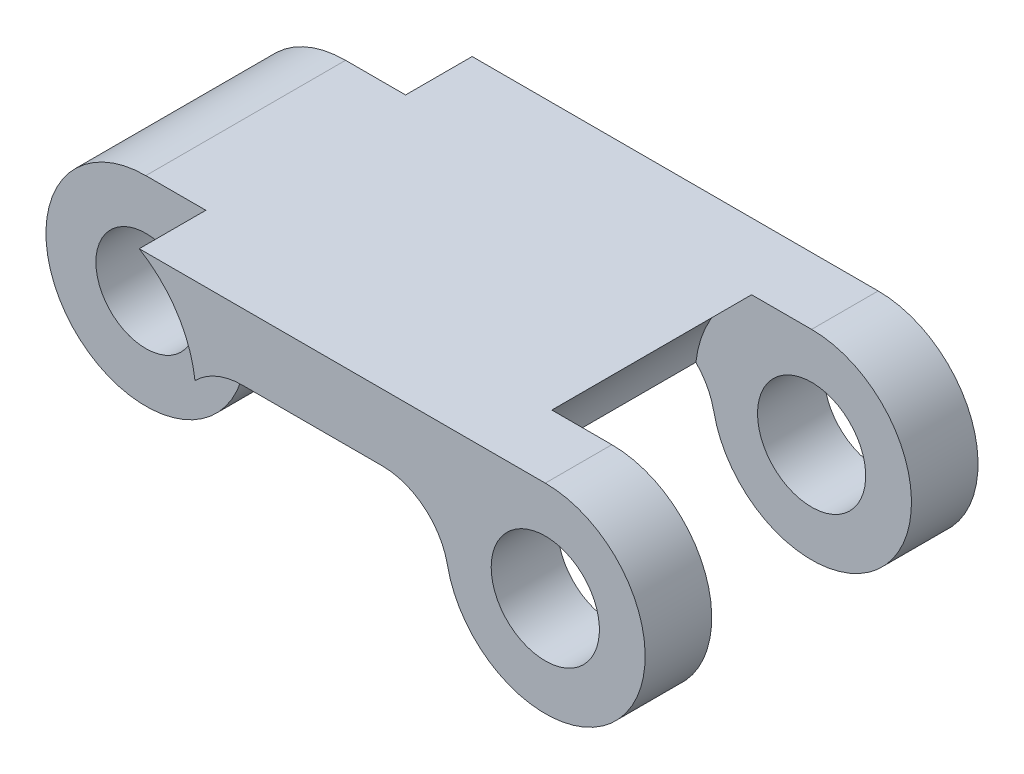
SolidWorks part; units mm, degrees
material "ABS PC"
ref_plane "Piano frontale" through (0, 0, 0) normal (0, 0, 1) x (1, 0, 0)
ref_plane "Piano superiore" through (0, 0, 0) normal (0, 1, 0) x (1, 0, 0)
ref_plane "Piano destro" through (0, 0, 0) normal (1, 0, 0) x (0, 0, -1)
sketch "Schizzo1" plane through (0, 0, 0) normal (0, 0, 1) x (1, 0, 0)
  line L0 (-24.825, 11.3137) -> (-10.825, 11.3137)
  line L1 (-21.9965, 9.3137) -> (-13.6534, 9.3137)
  arc A0 (-24.825, 11.3137) -> (-21.9965, 9.3137) centre (-24.825, 8.3137) ccw
  arc A1 (-10.825, 11.3137) -> (-13.6534, 9.3137) centre (-10.825, 8.3137) cw
  dimension "D1" = 3
  dimension "D2" = 3
  dimension "D3" = 2
  dimension "D5" = 14
extrude "Estrusione-Estrusione1" add sketch "Schizzo1" along normal blind 10
sketch "Schizzo5" plane through (0, 0, 0) normal (0, 0, -1) x (-1, 0, 0)
  circle A0 centre (10.825, 8.3137) radius 1.625
  circle A1 centre (24.825, 8.3137) radius 1.5
  arc A2 (21.9965, 9.3137) -> (24.825, 11.3137) centre (24.825, 8.3137) ccw construction
  arc A3 (10.825, 11.3137) -> (13.6534, 9.3137) centre (10.825, 8.3137) ccw construction
  dimension "D1" = 0
  dimension "D3" = 3.25
  dimension "D4" = 3
  dimension "D2" = 0
extrude "Taglio-Estrusione1" cut sketch "Schizzo5" against normal blind 10
sketch "Schizzo6" plane through (0, 0, 0) normal (0, 0, -1) x (-1, 0, 0)
  circle A0 centre (24.825, 8.3137) radius 3.5
  dimension "D1" = 7
extrude "Taglio-Estrusione2" cut sketch "Schizzo6" against normal blind 2
extrude "Taglio-Estrusione3" cut sketch "Schizzo6<2>" against normal blind 12 from offset 8 offset against normal yes
sketch "Schizzo6<2>" plane through (0, 0, 0) normal (0, 0, -1) x (-1, 0, 0) same geometry as "Schizzo6"
sketch "Schizzo7" plane through (0, 0, 0) normal (0, 0, -1) x (-1, 0, 0)
  circle A0 centre (10.825, 8.3137) radius 3.5
  dimension "D1" = 7
extrude "Taglio-Estrusione4" cut sketch "Schizzo7" against normal blind 6 from offset 2 offset against normal yes
fillet "Raccordo1" radius 2 1 edges at (-21.9965, 9.3137, 5)
fillet "Raccordo2" radius 2 1 edges at (-13.6534, 9.3137, 1)
